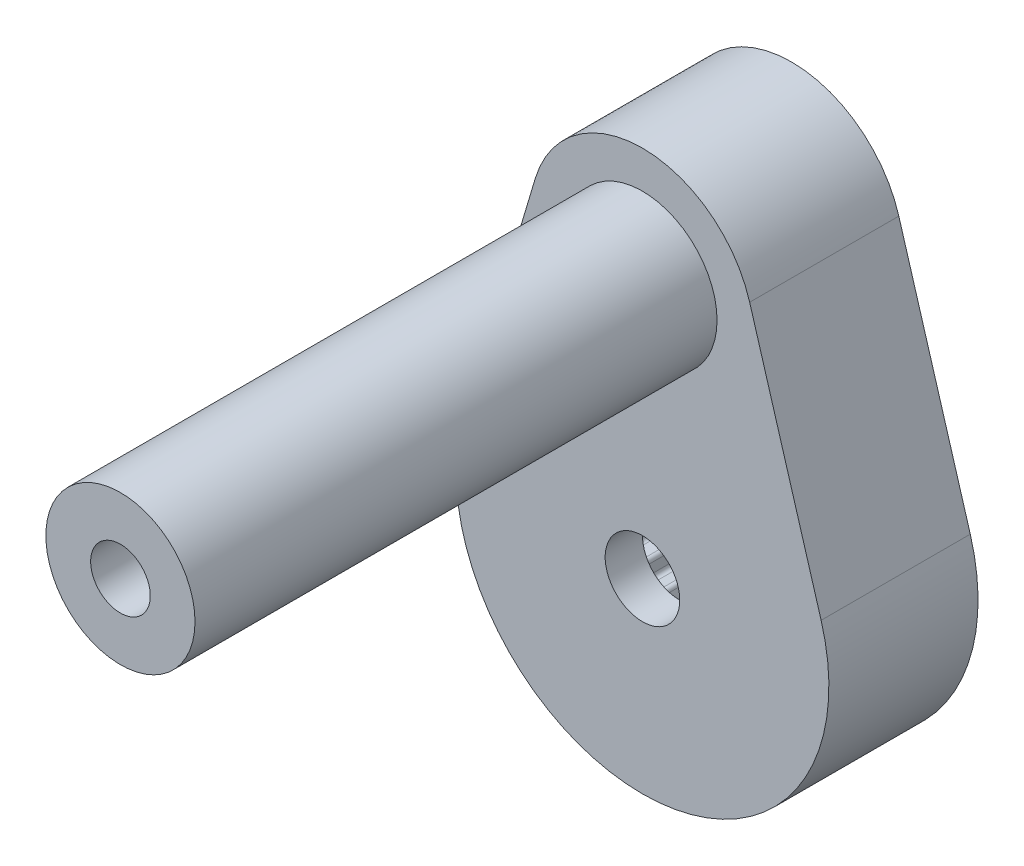
SolidWorks part; units mm, degrees
material "PVC hart"
ref_plane "Ebene vorne" through (0, 0, 0) normal (0, 0, 1) x (1, 0, 0)
ref_plane "Ebene oben" through (0, 0, 0) normal (0, 1, 0) x (1, 0, 0)
ref_plane "Ebene rechts" through (0, 0, 0) normal (1, 0, 0) x (0, 0, -1)
sketch "Skizze1" plane through (0, 0, 0) normal (0, 0, 1) x (1, 0, 0)
  line L0 (-4.7916, 1.4286) -> (-2.8749, 7.8571)
  line L1 (2.8749, 7.8571) -> (4.7916, 1.4286)
  line L2 (0, 7) -> (0, 0) construction
  circle A0 centre (0, 0) radius 2.9
  arc A1 (4.7916, 1.4286) -> (-4.7916, 1.4286) centre (0, 0) cw
  circle A2 centre (0, 7) radius 2
  circle A3 centre (0, 0) radius 1
  arc A4 (-2.8749, 7.8571) -> (2.8749, 7.8571) centre (0, 7) cw
  dimension "D1" = 5.8
  dimension "D2" = 5
  dimension "D4" = 4
  dimension "D5" = 2
  dimension "D6" = 1
  dimension "D3" = 7
extrude "Aufsatz-Linear austragen1" add sketch "Skizze1" against normal blind 3 contours A2 L0 A1 L1 A0 | A2 region at (-3.6605, 4.5913, 0) region at (0, 7, 0)
extrude "Aufsatz-Linear austragen2" add sketch "Skizze1<3>" along normal blind 1 contours A2 L0 A1 L1 A0 | A0 | A2 region at (-3.6605, 4.5913, 0) region at (-2.818, 0, 0) region at (0, 7, 0)
sketch "Skizze1<3>" plane through (0, 0, 0) normal (0, 0, 1) x (1, 0, 0) same geometry as "Skizze1"
extrude "Aufsatz-Linear austragen3" add sketch "Skizze1<4>" along normal blind 15 contours A2 region at (0, 7, 0)
sketch "Skizze1<4>" plane through (0, 0, 0) normal (0, 0, 1) x (1, 0, 0) same geometry as "Skizze1"
hole_wizard "Formsenkung für M3 Senkschraube mit Innensechskant1" positions "Skizze3" profile "Skizze2" countersink size "M3" standard "DIN" end condition through all
sketch "Skizze3" plane through (0.2004, -7.0436, -3) normal (0, 0, 1) x (1, 0, 0)
  arc A1 (2.6746, 14.9007) -> (-3.0753, 14.9007) centre (-0.2004, 14.0436) ccw construction
  point P0 (-0.2004, 14.0436)
sketch "Skizze2" plane through (0, 7, -3) normal (1, 0, 0) x (0, 1, 0)
  line L0 (0, 0) -> (0, 18)
  line L1 (0, 18) -> (0.8, 18)
  line L2 (0.8, 18) -> (0.8, 1.15)
  line L3 (0.8, 1.15) -> (1.95, 0)
  line L5 (1.95, 0) -> (0, 0)
  line L6 (-0.8, 1.15) -> (-1.95, 0) construction
  line L11 (0, -6.35) -> (0, 107.95) construction
  dimension "Bohrerdurchmesser" = 1.6
  dimension "Bohrungstiefe" = 18
  dimension "Senkdurchmesser (Oben)" = 3.9
  dimension "Senkwinkel (Oben)" = 90
ref_axis "Lenkachse" through (0, 7, 15) along (0, 0, -1)
ref_axis "Rotationsachse" through (0, 0, 1) along (0, 0, -1)
sketch "Skizze4" plane through (0, 0, -3) normal (0, 0, -1) x (-1, 0, 0)
  line L0 (0, 0) -> (-0.3635, 2.8771) construction
  line L1 (-0.2786, 2.847) -> (-0.0723, 2.6309)
  line L2 (0.2786, 2.847) -> (0.0723, 2.6309)
  line L3 (0.3635, 2.8771) -> (0, 0) construction
  line L4 (0, 2.9) -> (0, 0) construction
  circle A0 centre (0, 0) radius 2.9 construction
  circle A1 centre (0, 0) radius 2.9 construction
  arc A2 (-0.3635, 2.8771) -> (0.3635, 2.8771) centre (0, 0) cw
  circle A3 centre (0, 0) radius 2.6 construction
  arc A4 (-0.0723, 2.6309) -> (0.0723, 2.6309) centre (0, 2.7) ccw
  arc A5 (-0.3635, 2.8771) -> (-0.2786, 2.847) centre (-0.3509, 2.7779) cw
  arc A6 (0.3635, 2.8771) -> (0.2786, 2.847) centre (0.3509, 2.7779) ccw
  point P14 (0, 2.6)
  dimension "D2" = 5.2
  dimension "D3" = 0.1
  dimension "D1" = 14.4
extrude "Aufsatz-Linear austragen4" add sketch "Skizze4" against normal up to surface (3 mm away) up to face at (1, 0, 0)
pattern_circular "Kreismuster1" count 25 over 360 about axis through (0, 0, 1) along (0, 0, -1) of "Aufsatz-Linear austragen4"
